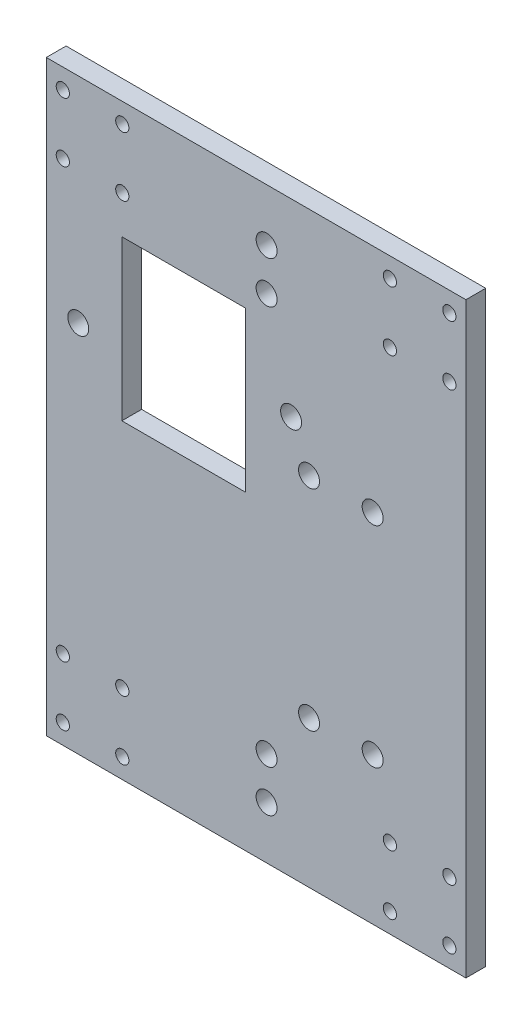
SolidWorks part; units mm, degrees
ref_plane "Front Plane" through (0, 0, 0) normal (0, 0, 1) x (1, 0, 0)
ref_plane "Top Plane" through (0, 0, 0) normal (0, 1, 0) x (1, 0, 0)
ref_plane "Right Plane" through (0, 0, 0) normal (1, 0, 0) x (0, 0, -1)
sketch "Sketch1" plane through (0, 0, 0) normal (0, 0, 1) x (1, 0, 0)
  line L1 (0, 0) -> (127, 0)
  line L2 (0, 0) -> (0, 177.8)
  line L3 (0, 177.8) -> (127, 177.8)
  line L4 (127, 0) -> (127, 177.8)
  line L5 (22.86, 142.24) -> (60.325, 142.24)
  line L6 (22.86, 142.24) -> (22.86, 93.98)
  line L7 (22.86, 93.98) -> (60.325, 93.98)
  line L8 (60.325, 142.24) -> (60.325, 93.98)
  circle A0 centre (5, 171.8) radius 2
  circle A1 centre (23, 171.8) radius 2
  circle A2 centre (5, 153.8) radius 2
  circle A3 centre (23, 153.8) radius 2
  circle A4 centre (104, 171.8) radius 2
  circle A5 centre (122, 171.8) radius 2
  circle A6 centre (104, 153.8) radius 2
  circle A7 centre (122, 153.8) radius 2
  circle A8 centre (23, 24) radius 2
  circle A9 centre (5, 24) radius 2
  circle A10 centre (5, 6) radius 2
  circle A11 centre (23, 6) radius 2
  circle A12 centre (122, 24) radius 2
  circle A13 centre (104, 24) radius 2
  circle A14 centre (104, 6) radius 2
  circle A15 centre (122, 6) radius 2
  circle A16 centre (98.7806, 44.45) radius 3.175
  circle A17 centre (79.5274, 44.45) radius 3.175
  circle A18 centre (79.5274, 107.95) radius 3.175
  circle A19 centre (98.7806, 107.95) radius 3.175
  circle A20 centre (9.6774, 113.03) radius 3.175
  circle A21 centre (74.0918, 120.65) radius 3.175
  circle A22 centre (66.675, 15.875) radius 3.175
  circle A23 centre (66.675, 161.925) radius 3.175
  circle A24 centre (66.675, 149.225) radius 3.175
  circle A25 centre (66.675, 28.575) radius 3.175
  dimension "D3" = 4
  dimension "D9" = 6
  dimension "D11" = 5
  dimension "D12" = 6.35
  dimension "D21" = 6.35
  dimension "D22" = 48.26
  dimension "D23" = 37.465
  dimension "D24" = 6.35
  dimension "D26" = 13.7668
  dimension "D27" = 6.35
  dimension "D28" = 60.325
  dimension "D29" = 15.875
  dimension "D30" = 15.875
  dimension "D1" = 127
  dimension "D2" = 177.8
  dimension "D4" = 18
  dimension "D5" = 18
  dimension "D6" = 18
  dimension "D7" = 18
  dimension "D8" = 6
  dimension "D10" = 5
  dimension "D13" = 44.45
  dimension "D14" = 107.95
  dimension "D15" = 28.2194
  dimension "D16" = 47.4726
  dimension "D17" = 22.86
  dimension "D18" = 13.1826
  dimension "D19" = 35.56
  dimension "D20" = 29.21
  dimension "D25" = 21.59
  dimension "D31" = 12.7
  dimension "D32" = 12.7
extrude "Boss-Extrude1" add sketch "Sketch1" along normal blind 5.9944
